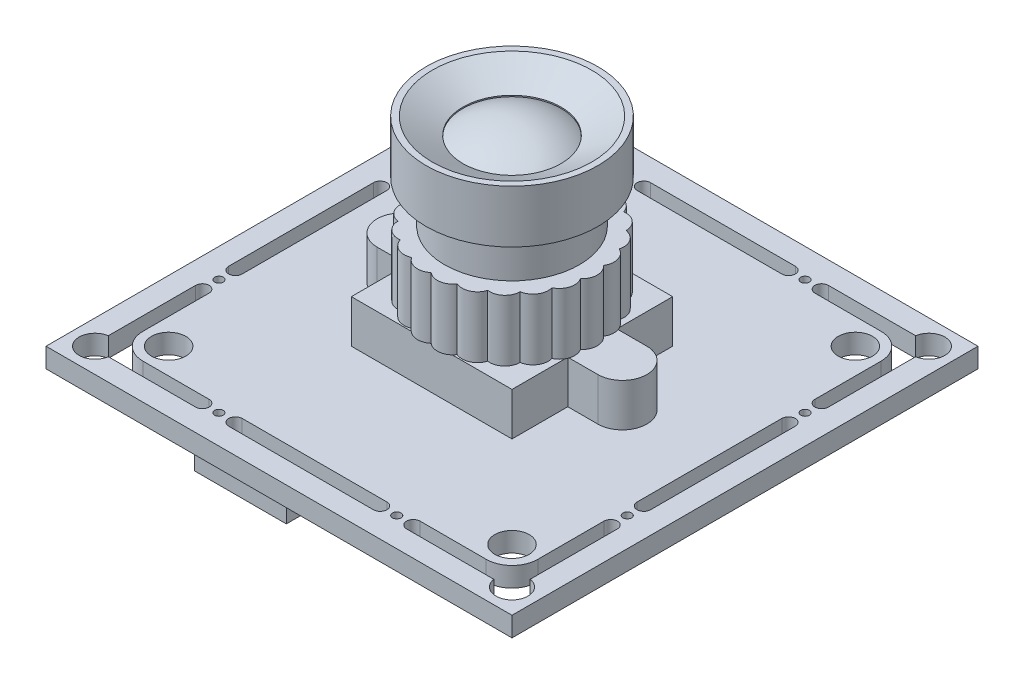
SolidWorks part; units mm, degrees
ref_plane "Front" through (0, 0, 0) normal (0, 0, 1) x (1, 0, 0)
ref_plane "Top" through (0, 0, 0) normal (0, 1, 0) x (1, 0, 0)
ref_plane "Right" through (0, 0, 0) normal (1, 0, 0) x (0, 0, -1)
sketch "Sketch1" plane through (0, 0, 0) normal (0, 1, 0) x (1, 0, 0)
  line L1 (19, -19) -> (-19, -19)
  line L2 (19, -19) -> (19, 19)
  line L3 (19, 19) -> (-19, 19)
  line L4 (-19, -19) -> (-19, 19)
  line L5 (19, -19) -> (-19, 19) construction
  line L6 (19, 19) -> (-19, -19) construction
  point P0 (0, 0)
  dimension "D1" = 38
extrude "Boss-Extrude1" add sketch "Sketch1" along normal blind 1.6
sketch "Sketch2" plane through (0, 1.6, 0) normal (0, 1, 0) x (1, 0, 0)
  line L0 (-6.55, 2) -> (-9, 2)
  line L1 (6.55, -6.55) -> (-6.55, -6.55)
  line L2 (6.55, -6.55) -> (6.55, -2)
  line L3 (6.55, 6.55) -> (-6.55, 6.55)
  line L4 (-6.55, -6.55) -> (-6.55, -2)
  line L5 (6.55, -6.55) -> (-6.55, 6.55) construction
  line L6 (6.55, 6.55) -> (-6.55, -6.55) construction
  line L7 (-9, -2) -> (-6.55, -2)
  line L8 (6.55, -2) -> (9, -2)
  line L9 (9, 2) -> (6.55, 2)
  line L10 (6.55, 2) -> (6.55, 6.55)
  line L11 (-6.55, 2) -> (-6.55, 6.55)
  arc A0 (-9, 2) -> (-9, -2) centre (-9, 0) ccw
  arc A1 (9, -2) -> (9, 2) centre (9, 0) ccw
  point P0 (0, 0)
  point P15 (0, 0)
  dimension "D2" = 18
  dimension "D1" = 13.1
  dimension "D3" = 4
extrude "Boss-Extrude2" add sketch "Sketch2" along normal blind 3.5
sketch "Sketch4" plane through (0, 0, 0) normal (0, 0, 1) x (1, 0, 0)
  line L0 (0, 0) -> (0, 17.65)
  line L1 (-4, 16.3946) -> (-4, 16.4946)
  line L2 (-4, 16.4946) -> (-6.5, 17.85)
  line L3 (-6.5, 17.85) -> (-7, 17.85)
  line L4 (-7, 17.85) -> (-7, 13.55)
  line L5 (-7, 13.55) -> (-5.5, 13.55)
  line L6 (-5.5, 13.55) -> (-5.5, 0)
  line L7 (-5.5, 0) -> (0, 0)
  line L8 (0, 0) -> (0, -1.5187) construction
  line L9 (-9, 5.1) -> (-11, 5.1) construction
  arc A0 (0, 17.65) -> (-4, 16.3946) centre (0, 10.65) ccw
  point P14 (0, 16.6975)
  point P15 (-4, 16.9517)
  point P16 (-4, 16.4843)
  point P17 (-4, 15.7207)
  point P18 (-4, 16.032)
  dimension "D8" = 0.1
  dimension "D9" = 7
  dimension "D1" = 11
  dimension "D2" = 8
  dimension "D3" = 4.3
  dimension "D4" = 12.75
  dimension "D5" = 0.5
  dimension "D6" = 14
  dimension "D7" = 0.2
revolve "Revolve1" add sketch "Sketch4" angle 360 about L8
sketch "Sketch3" plane through (0, 5.1, 0) normal (0, 1, 0) x (1, 0, 0)
  circle A0 centre (5.7, 0) radius 1.25
  circle A1 centre (0, 0) radius 6.95 construction
  circle A2 centre (5.4691, -1.6059) radius 1.25 construction
  circle A3 centre (4.7951, -3.0817) radius 1.25 construction
  circle A4 centre (3.7327, -4.3078) radius 1.25 construction
  circle A5 centre (2.3679, -5.1849) radius 1.25 construction
  circle A6 centre (0.8112, -5.642) radius 1.25 construction
  circle A7 centre (-0.8112, -5.642) radius 1.25 construction
  circle A8 centre (-2.3679, -5.1849) radius 1.25 construction
  circle A9 centre (-3.7327, -4.3078) radius 1.25 construction
  circle A10 centre (-4.7951, -3.0817) radius 1.25 construction
  circle A11 centre (-5.4691, -1.6059) radius 1.25 construction
  circle A12 centre (-5.7, 0) radius 1.25 construction
  circle A13 centre (-5.4691, 1.6059) radius 1.25 construction
  circle A14 centre (-4.7951, 3.0817) radius 1.25 construction
  circle A15 centre (-3.7327, 4.3078) radius 1.25 construction
  circle A16 centre (-2.3679, 5.1849) radius 1.25 construction
  circle A17 centre (-0.8112, 5.642) radius 1.25 construction
  circle A18 centre (0.8112, 5.642) radius 1.25 construction
  circle A19 centre (2.3679, 5.1849) radius 1.25 construction
  circle A20 centre (3.7327, 4.3078) radius 1.25 construction
  circle A21 centre (4.7951, 3.0817) radius 1.25 construction
  circle A22 centre (5.4691, 1.6059) radius 1.25 construction
  point P2 (-1.1005, 5.28)
  point P6 (0, 0)
  point P50 (0, 0)
  dimension "D2" = 13.9
  dimension "D3" = 2.5
  dimension "D1" = 22
extrude "Boss-Extrude3" add sketch "Sketch3" along normal blind 5
pattern_circular "CirPattern1" count 22 over 360 about axis through (0, 0, 0) along (0, 1, 0) of "Boss-Extrude3"
sketch "Sketch5" plane through (0, 0, 0) normal (0, -1, 0) x (1, 0, 0)
  line L0 (-19, -19) -> (-19, 19) construction
  line L1 (-10.5, 15.4) -> (-3, 15.4)
  line L2 (-10.5, 15.4) -> (-10.5, 11.65)
  line L3 (-10.5, 11.65) -> (-3, 11.65)
  line L4 (-3, 15.4) -> (-3, 11.65)
  line L5 (-19, 19) -> (19, 19) construction
  dimension "D1" = 7.5
  dimension "D2" = 3.75
  dimension "D3" = 8.5
  dimension "D4" = 3.6
extrude "Boss-Extrude4" add sketch "Sketch5" along normal blind 4.75
sketch "Sketch6" plane through (0, 1.6, 0) normal (0, 1, 0) x (1, 0, 0)
  line L0 (-15.7155, 17.2) -> (-8.6, 17.2)
  line L1 (-8.6, 16.1) -> (-14, 16.1)
  line L2 (-16.1, 14) -> (-16.1, 8.6)
  line L3 (-17.2, 8.6) -> (-17.2, 15.7155)
  line L4 (19, 19) -> (-19, 19) construction
  line L5 (0, 0) -> (0, 10.7558) construction
  line L6 (-5.9, 17.2) -> (5.9, 17.2)
  line L7 (5.9, 16.1) -> (-5.9, 16.1)
  line L9 (-8.6, 19) -> (-8.6, 17.2) construction
  line L10 (-19, 8.6) -> (-17.2, 8.6) construction
  line L11 (-19, 19) -> (-19, -19) construction
  line L12 (-8.6, 16.65) -> (-5.9, 16.65) construction
  line L13 (5.9, 16.65) -> (8.6, 16.65) construction
  line L14 (14, 16.1) -> (8.6, 16.1)
  line L15 (8.6, 17.2) -> (15.7155, 17.2)
  line L16 (17.2, 15.7155) -> (17.2, 8.6)
  line L17 (16.1, 8.6) -> (16.1, 14)
  line L18 (16.1, -5.9) -> (16.1, 5.9)
  line L19 (17.2, 5.9) -> (17.2, -5.9)
  line L20 (16.1, -14) -> (16.1, -8.6)
  line L21 (17.2, -8.6) -> (17.2, -15.7155)
  line L22 (15.7155, -17.2) -> (8.6, -17.2)
  line L23 (8.6, -16.1) -> (14, -16.1)
  line L24 (-5.9, -16.1) -> (5.9, -16.1)
  line L25 (5.9, -17.2) -> (-5.9, -17.2)
  line L26 (-14, -16.1) -> (-8.6, -16.1)
  line L27 (-8.6, -17.2) -> (-15.7155, -17.2)
  line L28 (-17.2, -15.7155) -> (-17.2, -8.6)
  line L29 (-16.1, -8.6) -> (-16.1, -14)
  line L30 (-16.1, 5.9) -> (-16.1, -5.9)
  line L31 (-17.2, -5.9) -> (-17.2, 5.9)
  line L32 (0, 0) -> (-13.1496, 0) construction
  arc A0 (-15.7155, 17.2) -> (-17.2, 15.7155) centre (-17, 17) ccw
  arc A1 (-8.6, 17.2) -> (-8.6, 16.1) centre (-8.6, 16.65) cw
  arc A2 (-14, 16.1) -> (-16.1, 14) centre (-14, 14) ccw
  arc A3 (-16.1, 8.6) -> (-17.2, 8.6) centre (-16.65, 8.6) cw
  circle A4 centre (-14, 14) radius 1.4
  arc A5 (5.9, 17.2) -> (5.9, 16.1) centre (5.9, 16.65) cw
  arc A6 (-5.9, 16.1) -> (-5.9, 17.2) centre (-5.9, 16.65) cw
  circle A7 centre (-7.25, 16.65) radius 0.35
  circle A8 centre (7.25, 16.65) radius 0.35
  circle A9 centre (14, 14) radius 1.4
  arc A10 (16.1, 14) -> (14, 16.1) centre (14, 14) ccw
  arc A11 (8.6, 16.1) -> (8.6, 17.2) centre (8.6, 16.65) cw
  arc A12 (17.2, 15.7155) -> (15.7155, 17.2) centre (17, 17) ccw
  arc A13 (17.2, 8.6) -> (16.1, 8.6) centre (16.65, 8.6) cw
  circle A14 centre (16.65, 7.25) radius 0.35
  arc A15 (16.1, 5.9) -> (17.2, 5.9) centre (16.65, 5.9) cw
  circle A16 centre (16.65, -7.25) radius 0.35
  arc A17 (17.2, -5.9) -> (16.1, -5.9) centre (16.65, -5.9) cw
  circle A18 centre (14, -14) radius 1.4
  arc A19 (14, -16.1) -> (16.1, -14) centre (14, -14) ccw
  arc A20 (16.1, -8.6) -> (17.2, -8.6) centre (16.65, -8.6) cw
  arc A21 (15.7155, -17.2) -> (17.2, -15.7155) centre (17, -17) ccw
  arc A22 (8.6, -17.2) -> (8.6, -16.1) centre (8.6, -16.65) cw
  circle A23 centre (7.25, -16.65) radius 0.35
  arc A24 (5.9, -16.1) -> (5.9, -17.2) centre (5.9, -16.65) cw
  circle A25 centre (-7.25, -16.65) radius 0.35
  arc A26 (-5.9, -17.2) -> (-5.9, -16.1) centre (-5.9, -16.65) cw
  circle A27 centre (-14, -14) radius 1.4
  arc A28 (-16.1, -14) -> (-14, -16.1) centre (-14, -14) ccw
  arc A29 (-8.6, -16.1) -> (-8.6, -17.2) centre (-8.6, -16.65) cw
  arc A30 (-17.2, -15.7155) -> (-15.7155, -17.2) centre (-17, -17) ccw
  arc A31 (-17.2, -8.6) -> (-16.1, -8.6) centre (-16.65, -8.6) cw
  circle A32 centre (-16.65, -7.25) radius 0.35
  arc A33 (-16.1, -5.9) -> (-17.2, -5.9) centre (-16.65, -5.9) cw
  circle A34 centre (-16.65, 7.25) radius 0.35
  arc A35 (-17.2, 5.9) -> (-16.1, 5.9) centre (-16.65, 5.9) cw
  dimension "D1" = 2.6
  dimension "D4" = 34
  dimension "D5" = 2.8
  dimension "D6" = 28
  dimension "D7" = 1.6
  dimension "D8" = 14.5
  dimension "D9" = 0.7
  dimension "D11" = 34
  dimension "D2" = 1.1
  dimension "D3" = 1.8
  dimension "D10" = 4
extrude "Cut-Extrude1" cut sketch "Sketch6" against normal through all
